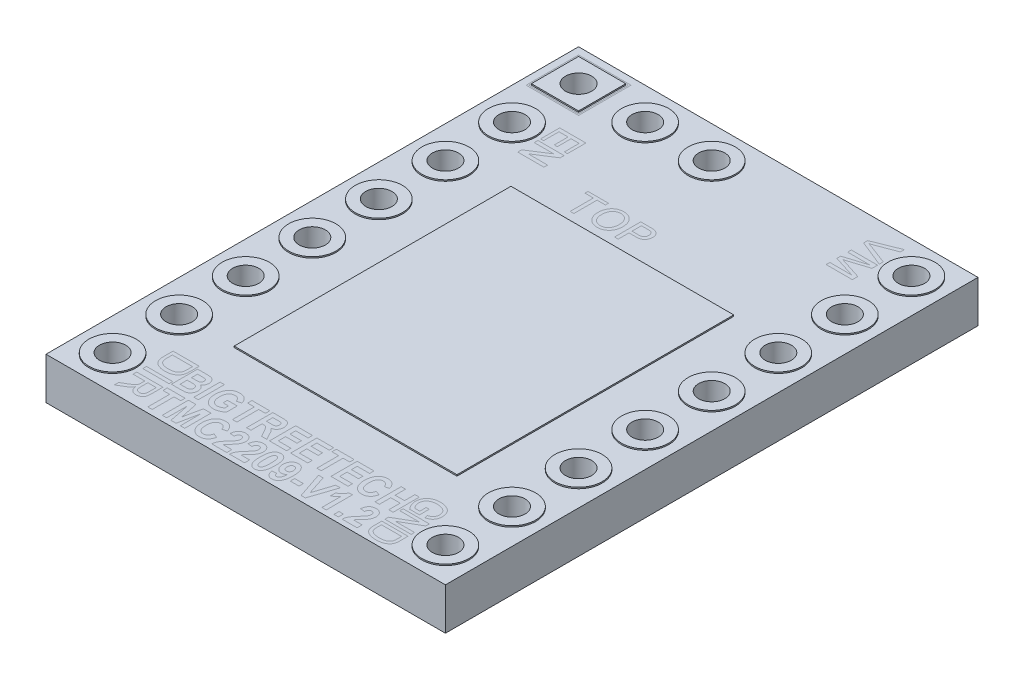
SolidWorks part; units mm, degrees
ref_plane "Ebene vorne" through (0, 0, 0) normal (0, 0, 1) x (1, 0, 0)
ref_plane "Ebene oben" through (0, 0, 0) normal (0, 1, 0) x (1, 0, 0)
ref_plane "Ebene rechts" through (0, 0, 0) normal (1, 0, 0) x (0, 0, -1)
sketch "Skizze2" plane through (0, 0, 0) normal (0, 1, 0) x (1, 0, 0)
  line L1 (-7.62, -10.16) -> (7.62, -10.16)
  line L2 (-7.62, -10.16) -> (-7.62, 10.16)
  line L3 (-7.62, 10.16) -> (7.62, 10.16)
  line L4 (7.62, -10.16) -> (7.62, 10.16)
  line L5 (-7.62, -10.16) -> (7.62, 10.16) construction
  line L6 (-7.62, 10.16) -> (7.62, -10.16) construction
  point P0 (0, 0)
  dimension "D1" = 15.24
  dimension "D2" = 20.32
extrude "Aufsatz-Linear austragen1" add sketch "Skizze2" along normal blind 1.6
sketch "Skizze3" plane through (0, 1.6, 0) normal (0, 1, 0) x (1, 0, 0)
  line L0 (-6.35, 10.16) -> (-6.35, -10.16) construction
  line L1 (7.62, 10.16) -> (-7.62, 10.16) construction
  line L2 (-7.62, -10.16) -> (7.62, -10.16) construction
  line L3 (-3.81, 10.16) -> (-3.81, -10.16) construction
  line L4 (-1.27, 10.16) -> (-1.27, -10.16) construction
  line L5 (1.27, 10.16) -> (1.27, -10.16) construction
  line L6 (3.81, 10.16) -> (3.81, -10.16) construction
  line L7 (6.35, 10.16) -> (6.35, -10.16) construction
  line L8 (-6.35, 10.16) -> (-3.81, 10.16) construction
  line L10 (0, -1000) -> (0, 49000) construction
  line L11 (-7.62, -8.89) -> (7.62, -8.89) construction
  line L12 (-7.62, 10.16) -> (-7.62, -10.16) construction
  line L13 (7.62, -10.16) -> (7.62, 10.16) construction
  line L14 (-7.62, -6.35) -> (7.62, -6.35) construction
  line L15 (-7.62, -3.81) -> (7.62, -3.81) construction
  line L16 (-7.62, -1.27) -> (7.62, -1.27) construction
  line L17 (-7.62, 1.27) -> (7.62, 1.27) construction
  line L18 (-7.62, 3.81) -> (7.62, 3.81) construction
  line L19 (-7.62, 6.35) -> (7.62, 6.35) construction
  line L20 (-7.62, 8.89) -> (7.62, 8.89) construction
  line L21 (-1000, 0) -> (49000, 0) construction
  circle A0 centre (-6.35, -8.89) radius 0.5
  circle A1 centre (6.35, -8.89) radius 0.5
  circle A2 centre (6.35, -6.35) radius 0.5
  circle A3 centre (6.35, -3.81) radius 0.5
  circle A4 centre (6.35, -1.27) radius 0.5
  circle A5 centre (6.35, 1.27) radius 0.5
  circle A6 centre (6.35, 3.81) radius 0.5
  circle A7 centre (6.35, 6.35) radius 0.5
  circle A8 centre (6.35, 8.89) radius 0.5
  circle A9 centre (-6.35, -6.35) radius 0.5
  circle A10 centre (-6.35, -3.81) radius 0.5
  circle A11 centre (-6.35, -1.27) radius 0.5
  circle A12 centre (-6.35, 1.27) radius 0.5
  circle A13 centre (-6.35, 3.81) radius 0.5
  circle A14 centre (-6.35, 6.35) radius 0.5
  circle A15 centre (-6.35, 8.89) radius 0.5
  circle A16 centre (-3.81, 8.89) radius 0.5
  circle A17 centre (-1.27, 8.89) radius 0.5
  point P77 (-1.27, 8.89)
  dimension "D5" = 1
  dimension "D2" = 2.54
  dimension "D3" = 8
  dimension "D4" = 2.54
  dimension "D1" = 6
  dimension "D6" = 2
  dimension "D7" = 8
  dimension "D8" = 3
extrude "Schnitt-Linear austragen1" cut sketch "Skizze3" against normal up to surface (1.6 mm away) up to face at (0, 0, 0)
sketch "Skizze4" plane through (0, 1.6, 0) normal (0, 1, 0) x (1, 0, 0)
  line L0 (-7.62, -8.76) -> (7.62, -8.76) construction
  line L1 (-7.62, 10.16) -> (-7.62, -10.16) construction
  line L2 (7.62, -10.16) -> (7.62, 10.16) construction
  line L3 (-7.62, -9.96) -> (7.62, -9.96) construction
  line L4 (-7.62, -10.16) -> (7.62, -10.16) construction
  line L5 (-5.3, -7.46) -> (-5.3, -9.96) construction
  line L6 (-7.25, 7.99) -> (-5.45, 7.99) construction
  line L7 (-7.25, 7.99) -> (-7.25, 9.79) construction
  line L8 (-7.25, 9.79) -> (-5.45, 9.79) construction
  line L9 (-5.45, 7.99) -> (-5.45, 9.79) construction
  line L10 (-7.25, 7.99) -> (-5.45, 9.79) construction
  line L11 (-7.25, 9.79) -> (-5.45, 7.99) construction
  line L12 (4.3, -7.46) -> (4.3, -9.96) construction
  line L13 (-5.4, 7.94) -> (-5.4, 9.84)
  line L14 (-7.3, 9.84) -> (-5.4, 9.84)
  line L15 (-7.3, 7.94) -> (-7.3, 9.84)
  line L16 (-7.3, 7.94) -> (-5.4, 7.94)
  line L17 (-7.35, 7.89) -> (-7.35, 9.89)
  line L18 (-7.35, 9.89) -> (-5.35, 9.89)
  line L19 (-5.35, 7.89) -> (-5.35, 9.89)
  line L20 (-7.35, 7.89) -> (-5.35, 7.89)
  line L21 (-5.3, 7.2343) -> (-5.3, 5.4657) construction
  line L22 (-3.0277, 4.56) -> (0.4877, 4.56) construction
  line L23 (7.62, 10.16) -> (-7.62, 10.16) construction
  line L24 (4.3, 9.66) -> (4.3, 7.66) construction
  line L25 (-4.25, -6.35) -> (4.25, -6.35) construction
  line L26 (-4.25, -6.35) -> (-4.25, 4.31) construction
  line L27 (-4.25, 4.31) -> (4.25, 4.31) construction
  line L28 (4.25, -6.35) -> (4.25, 4.31) construction
  line L29 (-4.25, -6.35) -> (4.25, 4.31) construction
  line L30 (-4.25, 4.31) -> (4.25, -6.35) construction
  circle A0 centre (-6.35, -8.89) radius 0.9 construction
  circle A1 centre (6.35, -8.89) radius 0.9 construction
  circle A2 centre (6.35, -6.35) radius 0.9 construction
  circle A3 centre (6.35, -3.81) radius 0.9 construction
  circle A4 centre (6.35, -1.27) radius 0.9 construction
  circle A5 centre (6.35, 1.27) radius 0.9 construction
  circle A6 centre (6.35, 3.81) radius 0.9 construction
  circle A7 centre (6.35, 6.35) radius 0.9 construction
  circle A8 centre (6.35, 8.89) radius 0.9 construction
  circle A9 centre (-6.35, -6.35) radius 0.9 construction
  circle A10 centre (-6.35, -3.81) radius 0.9 construction
  circle A11 centre (-6.35, -1.27) radius 0.9 construction
  circle A12 centre (-6.35, 1.27) radius 0.9 construction
  circle A13 centre (-6.35, 3.81) radius 0.9 construction
  circle A14 centre (-6.35, 6.35) radius 0.9 construction
  circle A15 centre (-6.35, 8.89) radius 0.9 construction
  circle A16 centre (-6.35, 8.89) radius 0.5 construction
  circle A17 centre (-6.35, 3.81) radius 0.5 construction
  circle A19 centre (-3.81, 8.89) radius 0.9 construction
  circle A20 centre (-1.27, 8.89) radius 0.9 construction
  text T2 "DIR" font "Arial" height 1
  text T3 "GND" font "Arial" height 1
  text T4 "EN" font "Arial" height 1
  text T5 "TOP" font "Arial" height 1
  text T6 "VM" font "Arial" height 1
  point P73 (-5.3, 6.35)
  point P77 (-1.27, 4.56)
  point P78 (4.3, 9.6619)
  point P79 (4.3, 9.6619)
  point P80 (0, -1.02)
  point P89 (4.3, 7.7167)
  dimension "D3" = 1.8
  dimension "D2" = 0.2
  dimension "D7" = 2.5
  dimension "D8" = 0.15
  dimension "D9" = 1.15
  dimension "D12" = 5.6
  dimension "D13" = 8.5
  dimension "D14" = 0.5
  dimension "D15" = 2
  dimension "D1" = 1.2
  dimension "D10" = 0.05
  dimension "D11" = 0.05
  dimension "D4" = 2
  dimension "D5" = 8
  dimension "D6" = 3
sketch "Skizze5" plane through (0, 1.6, 0) normal (0, 1, 0) x (1, 0, 0)
  line L8 (-7.25, 7.99) -> (-5.45, 7.99)
  line L9 (-5.45, 7.99) -> (-5.45, 9.79)
  line L10 (-5.45, 9.79) -> (-7.25, 9.79)
  line L11 (-7.25, 9.79) -> (-7.25, 7.99)
  line L16 (-7.35, 9.89) -> (-7.35, 7.89)
  line L17 (-5.35, 9.89) -> (-7.35, 9.89)
  line L18 (-5.35, 7.89) -> (-5.35, 9.89)
  line L19 (-7.35, 7.89) -> (-5.35, 7.89)
  line L24 (-7.3, 9.84) -> (-7.3, 7.94)
  line L25 (-7.3, 7.94) -> (-5.4, 7.94)
  line L26 (-5.4, 7.94) -> (-5.4, 9.84)
  line L27 (-5.4, 9.84) -> (-7.3, 9.84)
  line L32 (-4.25, -6.35) -> (4.25, -6.35)
  line L33 (4.25, -6.35) -> (4.25, 4.21)
  line L34 (4.25, 4.21) -> (-4.25, 4.21)
  line L35 (-4.25, 4.21) -> (-4.25, -6.35)
  circle A2 centre (-6.35, -8.89) radius 0.9
  circle A4 centre (6.35, 6.35) radius 0.9
  circle A6 centre (6.35, 3.81) radius 0.9
  circle A8 centre (6.35, 1.27) radius 0.9
  circle A10 centre (6.35, -1.27) radius 0.9
  circle A12 centre (6.35, -3.81) radius 0.9
  circle A14 centre (6.35, -6.35) radius 0.9
  circle A16 centre (6.35, -8.89) radius 0.9
  circle A18 centre (-6.35, 6.35) radius 0.9
  circle A20 centre (-6.35, 3.81) radius 0.9
  circle A22 centre (-6.35, 1.27) radius 0.9
  circle A24 centre (-6.35, -1.27) radius 0.9
  circle A26 centre (-6.35, -3.81) radius 0.9
  circle A28 centre (-6.35, -6.35) radius 0.9
  circle A30 centre (6.35, 8.89) radius 0.9
  circle A32 centre (-1.27, 8.89) radius 0.9
  circle A34 centre (-3.81, 8.89) radius 0.9
  circle M34 centre (-6.35, -1.27) radius 0.5
  circle M35 centre (-6.35, -3.81) radius 0.5
  circle M36 centre (-6.35, -6.35) radius 0.5
  circle M37 centre (6.35, 8.89) radius 0.5
  circle M38 centre (-6.35, 1.27) radius 0.5
  circle M39 centre (-6.35, 3.81) radius 0.5
  circle M40 centre (-6.35, 6.35) radius 0.5
  circle M41 centre (-6.35, 8.89) radius 0.5
  circle M42 centre (6.35, -3.81) radius 0.5
  circle M43 centre (6.35, -6.35) radius 0.5
  circle M44 centre (6.35, -8.89) radius 0.5
  circle M45 centre (-3.81, 8.89) radius 0.5
  circle M46 centre (6.35, -1.27) radius 0.5
  circle M47 centre (6.35, 1.27) radius 0.5
  circle M48 centre (6.35, 3.81) radius 0.5
  circle M49 centre (6.35, 6.35) radius 0.5
  circle M50 centre (-1.27, 8.89) radius 0.5
  circle M51 centre (-6.35, -8.89) radius 0.5
wrap "Umwickeln1" sketch "Skizze4" wrap type scribe source sketch "Skizze4" face at (-6.35, 1.6, 1.77)
extrude "Aufsatz-Linear austragen2" add sketch "Skizze5" along normal blind 0.05 contours A2 M51 | A28 M36 | A26 M35 | A24 M34 | A22 M38 | A20 M39 | A18 M40 | L10 L11 L8 L9 M41 | A34 M45 | A32 M50 | A30 M37 | A4 M49 | A6 M48 | A8 M47 | A10 M46 | A12 M42 | A14 M43 | A16 M44 | L32 L33 L34 L35 region at (-7.2245, 1.6, -8.89) region at (-7.2245, 1.6, 8.89) region at (5.4755, 1.6, -6.35) region at (5.4755, 1.6, -3.81) region at (5.4755, 1.6, -1.27) region at (5.4755, 1.6, 1.27) region at (5.4755, 1.6, 3.81) region at (5.4755, 1.6, 6.35) region at (5.4755, 1.6, 8.89) region at (-7.2245, 1.6, -6.35) region at (-7.2245, 1.6, -3.81) region at (-7.2245, 1.6, -1.27) region at (-7.2245, 1.6, 1.27) region at (-7.2245, 1.6, 3.81) region at (-7.2245, 1.6, 6.35) region at (5.4755, 1.6, -8.89) region at (-2.1445, 1.6, -8.89) region at (-4.6845, 1.6, -8.89)
sketch "Skizze6" plane through (0, 1.6, 0) normal (0, 1, 0) x (1, 0, 0)
  line L0 (-7.62, -9.96) -> (7.62, -9.96) construction
  line L1 (-7.62, -8.76) -> (7.62, -8.76) construction
  line L2 (-7.62, -9.96) -> (7.62, -9.96) construction
  line L3 (-7.62, -8.76) -> (7.62, -8.76) construction
  text T0 "<b>BIGTREETECH</b>" font "Arial" height 1
  text T1 "<b>TMC2209-V1.2</b>" font "Arial" height 1
wrap "Umwickeln2" sketch "Skizze6" wrap type scribe source sketch "Skizze6" face at (4.7298, 1.6, -8.1693)
